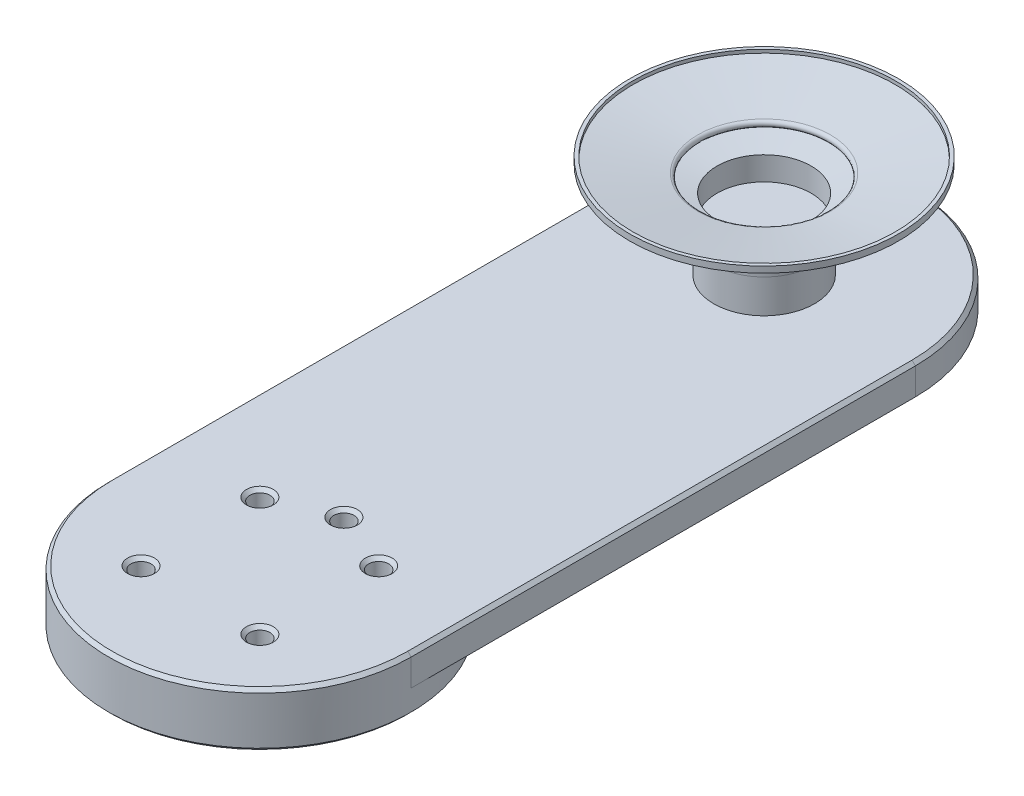
SolidWorks part; units mm, degrees
other "Greifer"
other "Distanzring"
other "Messingring"
other "Flanschplatte"
ref_plane "Ebene vorne" through (0, 0, 0) normal (0, 0, 1) x (1, 0, 0)
ref_plane "Ebene oben" through (0, 0, 0) normal (0, 1, 0) x (1, 0, 0)
ref_plane "Ebene rechts" through (0, 0, 0) normal (1, 0, 0) x (0, 0, -1)
sketch "Skizze2" plane through (0, 0, 0) normal (0, 1, 0) x (1, 0, 0)
  circle A0 centre (0, 0) radius 45
  circle A1 centre (0, 0) radius 31.5
  dimension "D1" = 90
  dimension "D2" = 63
extrude "Aufsatz-Linear austragen1" add sketch "Skizze2" along normal blind 6.2
sketch "Skizze3" plane through (0, 6.2, 0) normal (0, 1, 0) x (1, 0, 0)
  line L0 (0, 0) -> (0, 25) construction
  line L1 (-45, 0) -> (-45, 150)
  line L2 (17.6777, 17.6777) -> (0, 0) construction
  line L3 (45, 150) -> (45, 0)
  circle A2 centre (0, 25) radius 3
  circle A3 centre (17.6777, 17.6777) radius 3
  circle A4 centre (17.6777, -17.6777) radius 3
  circle A5 centre (-17.6777, -17.6777) radius 3
  circle A6 centre (-17.6777, 17.6777) radius 3
  arc A7 (-45, 150) -> (45, 150) centre (0, 150) cw
  arc A8 (-45, 0) -> (45, 0) centre (0, 0) ccw
  circle A9 centre (0, 0) radius 45 construction
  circle A10 centre (0, 150) radius 6
  point P18 (0, 0)
  dimension "D3" = 6
  dimension "D7" = 12
  dimension "D1" = 25
  dimension "D2" = 25
  dimension "D4" = 45
  dimension "D6" = 150
  dimension "D5" = 4
extrude "Aufsatz-Linear austragen2" add sketch "Skizze3" along normal blind 10
sketch "Skizze4" plane through (0, 16.2, 0) normal (0, 1, 0) x (1, 0, 0)
  circle A0 centre (0, 150) radius 6 construction
  circle A1 centre (0, 150) radius 6
  circle A2 centre (0, 150) radius 15
  dimension "D1" = 30
extrude "Aufsatz-Linear austragen3" add sketch "Skizze4" along normal blind 10 separate body
sketch "Skizze5" plane through (0, 26.2, 0) normal (0, 1, 0) x (1, 0, 0)
  circle A0 centre (0, 150) radius 6 construction
  circle A1 centre (0, 150) radius 15 construction
  circle A2 centre (0, 150) radius 6
  circle A3 centre (0, 150) radius 15
extrude "Aufsatz-Linear austragen4" add sketch "Skizze5" along normal blind 3 separate body
ref_axis "Achse1" through (0, 29.2, -150) along (0, -1, 0)
ref_plane "Ebene1" through (0, 0, -150) normal (0, 0, 1) x (0, -1, 0)
sketch "Skizze6" plane through (0, 0, -150) normal (0, 0, 1) x (0, -1, 0)
  line L0 (-30.2, 0) -> (-30.2, 14)
  line L1 (-30.2, 14) -> (-37.21, 14)
  line L6 (-29.2, 15) -> (-36.3674, 15)
  line L7 (-36.3674, 15) -> (-39.3035, 32.0585)
  line L8 (-39.3035, 32.0585) -> (-41.397, 19.8954)
  line L9 (-41.397, 19.8954) -> (-44.8574, 40)
  line L10 (-44.8574, 40) -> (-46.7, 40)
  line L13 (-29.2, 15) -> (-29.2, -15) construction
  line L14 (-29.2, 0) -> (-29.2, 15)
  line L15 (-37.21, 14) -> (-39.3035, 26.1631)
  line L16 (-39.3035, 26.1631) -> (-41.397, 14)
  line L17 (-41.397, 14) -> (-45.7, 39)
  line L18 (-45.7, 39) -> (-46.7, 39)
  line L19 (-46.7, 40) -> (-46.7, 39)
  line L21 (-29.2, 0) -> (-30.2, 0)
  point P0 (-44.5617, 40)
  dimension "D2" = 17.5
  dimension "D1" = 40
  dimension "D3" = 1
revolve "Rotation1" add sketch "Skizze6" angle 360 about axis through (0, 29.2, -150) along (0, -1, 0)
fillet "Verrundung1" radius 1 2 edges at (0, 41.397, -136) (0, 39.3035, -117.9415)
chamfer "Fase1" distance 1 angle 45 20 edges at (0, 16.2, -144) (-17.6777, 16.2, 20.6777) (17.6777, 16.2, -14.6777) (-45, 16.2, -75) (0, 16.2, -195) (45, 16.2, -75) (0, 16.2, 45) (0, 16.2, -22) (17.6777, 16.2, 20.6777) (-17.6777, 16.2, -14.6777) (-17.6777, 6.2, -14.6777) (0, 6.2, -22) (17.6777, 6.2, -14.6777) (17.6777, 6.2, 20.6777) (-17.6777, 6.2, 20.6777) (-45, 6.2, -75) (0, 6.2, -195) (45, 6.2, -75) (0, 0, 45) (0, 0, 31.5)
